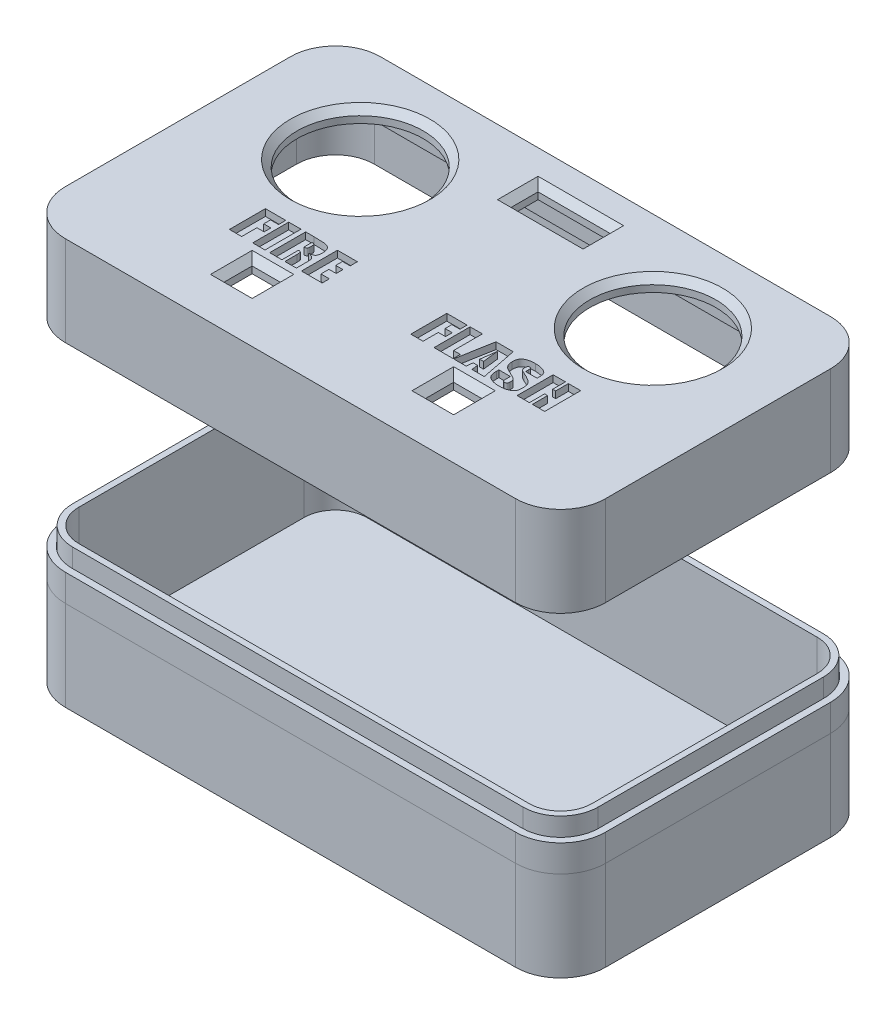
SolidWorks part; units mm, degrees
ref_plane "Front Plane" through (0, 0, 0) normal (0, 0, 1) x (1, 0, 0)
ref_plane "Top Plane" through (0, 0, 0) normal (0, 1, 0) x (1, 0, 0)
ref_plane "Right Plane" through (0, 0, 0) normal (1, 0, 0) x (0, 0, -1)
sketch "Sketch1" plane through (0, 0, 0) normal (0, 1, 0) x (1, 0, 0)
  line L1 (-60, 35) -> (60, 35)
  line L2 (-60, 35) -> (-60, -35)
  line L3 (-60, -35) -> (60, -35)
  line L4 (60, 35) -> (60, -35)
  line L5 (-60, 35) -> (60, -35) construction
  line L6 (-60, -35) -> (60, 35) construction
  point P0 (0, 0)
  dimension "D1" = 120
  dimension "D2" = 70
extrude "Boss-Extrude1" add sketch "Sketch1" along normal blind 20
fillet "Fillet1" radius 10 4 edges at (-60, 10, -35) (60, 10, -35) (60, 10, 35) (-60, 10, 35)
shell "Shell1" thickness 3 removed face at (0, 0, 0)
sketch "Sketch2" plane through (0, 20, 0) normal (0, 1, 0) x (1, 0, 0)
  line L0 (50, 35) -> (-50, 35) construction
  line L13 (-25.5, -18) -> (-19.25, -18)
  line L14 (-25.5, -18) -> (-25.5, -24.25)
  line L15 (-25.5, -24.25) -> (-19.25, -24.25)
  line L16 (-19.25, -18) -> (-19.25, -24.25)
  line L17 (-25.5, -18) -> (-19.25, -24.25) construction
  line L18 (-25.5, -24.25) -> (-19.25, -18) construction
  line L19 (19.25, -18) -> (25.5, -18)
  line L20 (19.25, -18) -> (19.25, -24.25)
  line L21 (19.25, -24.25) -> (25.5, -24.25)
  line L22 (25.5, -18) -> (25.5, -24.25)
  line L23 (19.25, -18) -> (25.5, -24.25) construction
  line L24 (19.25, -24.25) -> (25.5, -18) construction
  circle A0 centre (-32.5, 13) radius 14
  circle A1 centre (32.5, 13) radius 14
  point P0 (-32.5, 13)
  point P5 (32.5, 13)
  point P10 (-22.375, -21.125)
  point P15 (22.375, -21.125)
  dimension "D1" = 28
  dimension "D2" = 28
  dimension "D5" = 6.25
  dimension "D7" = 18
  dimension "D3" = 65
  dimension "D4" = 32.5
  dimension "D6" = 22
  dimension "D8" = 38.5
  dimension "D9" = 19.25
extrude "Cut-Extrude1" cut sketch "Sketch2" against normal up to next
sketch "Sketch5" plane through (0, 0, 0) normal (0, -1, 0) x (1, 0, 0)
  line L28 (50, 33.65) -> (-50, 33.65)
  line L29 (-58.65, 25) -> (-58.65, -25)
  line L30 (-50, -33.65) -> (50, -33.65)
  line L31 (58.65, -25) -> (58.65, 25)
  line L32 (50, 33.65) -> (-50, 33.65)
  line L33 (-58.65, 25) -> (-58.65, -25)
  line L34 (-50, -33.65) -> (50, -33.65)
  line L35 (58.65, -25) -> (58.65, 25)
  arc A23 (58.65, 25) -> (50, 33.65) centre (50, 25) ccw
  arc A24 (-50, 33.65) -> (-58.65, 25) centre (-50, 25) ccw
  arc A25 (-58.65, -25) -> (-50, -33.65) centre (-50, -25) ccw
  arc A26 (50, -33.65) -> (58.65, -25) centre (50, -25) ccw
  arc A27 (58.65, 25) -> (50, 33.65) centre (50, 25) ccw
  arc A28 (-50, 33.65) -> (-58.65, 25) centre (-50, 25) ccw
  arc A29 (-58.65, -25) -> (-50, -33.65) centre (-50, -25) ccw
  arc A30 (50, -33.65) -> (58.65, -25) centre (50, -25) ccw
  dimension "D1" = 1.35
extrude "Cut-Extrude3" cut sketch "Sketch5" against normal blind 10
ref_plane "Plane1" through (0, -40.15, 0) normal (0, -1, 0) x (-1, 0, 0)
sketch "Sketch6" plane through (0, -40.15, 0) normal (0, -1, 0) x (-1, 0, 0)
  line L4 (60, -25) -> (60, 25)
  line L5 (50, 35) -> (-50, 35)
  line L6 (-60, 25) -> (-60, -25)
  line L7 (-50, -35) -> (50, -35)
  line L8 (60, -25) -> (60, 25)
  line L9 (50, 35) -> (-50, 35)
  line L10 (-60, 25) -> (-60, -25)
  line L11 (-50, -35) -> (50, -35)
  arc A4 (60, 25) -> (50, 35) centre (50, 25) ccw
  arc A5 (-50, 35) -> (-60, 25) centre (-50, 25) ccw
  arc A6 (-60, -25) -> (-50, -35) centre (-50, -25) ccw
  arc A7 (50, -35) -> (60, -25) centre (50, -25) ccw
  arc A8 (60, 25) -> (50, 35) centre (50, 25) ccw
  arc A9 (-50, 35) -> (-60, 25) centre (-50, 25) ccw
  arc A10 (-60, -25) -> (-50, -35) centre (-50, -25) ccw
  arc A11 (50, -35) -> (60, -25) centre (50, -25) ccw
  dimension "D1" = 0
extrude "Boss-Extrude2" add sketch "Sketch6" along normal blind 30 separate body
shell "Shell2" thickness 3 removed face at (0, -40.15, 0)
sketch "Sketch7" plane through (0, -40.15, 0) normal (0, 1, 0) x (1, 0, 0)
  line L8 (-50, -33.35) -> (50, -33.35)
  line L9 (58.35, -25) -> (58.35, 25)
  line L10 (50, 33.35) -> (-50, 33.35)
  line L11 (-58.35, 25) -> (-58.35, -25)
  line L12 (-50, -33.35) -> (50, -33.35)
  line L13 (58.35, -25) -> (58.35, 25)
  line L14 (50, 33.35) -> (-50, 33.35)
  line L15 (-58.35, 25) -> (-58.35, -25)
  line L20 (-50, -36.5) -> (50, -36.5)
  line L21 (61.5, -25) -> (61.5, 25)
  line L22 (50, 36.5) -> (-50, 36.5)
  line L23 (-61.5, 25) -> (-61.5, -25)
  line L24 (-50, -36.5) -> (50, -36.5)
  line L25 (61.5, -25) -> (61.5, 25)
  line L26 (50, 36.5) -> (-50, 36.5)
  line L27 (-61.5, 25) -> (-61.5, -25)
  arc A8 (-58.35, -25) -> (-50, -33.35) centre (-50, -25) ccw
  arc A9 (50, -33.35) -> (58.35, -25) centre (50, -25) ccw
  arc A10 (58.35, 25) -> (50, 33.35) centre (50, 25) ccw
  arc A11 (-50, 33.35) -> (-58.35, 25) centre (-50, 25) ccw
  arc A12 (-58.35, -25) -> (-50, -33.35) centre (-50, -25) ccw
  arc A13 (50, -33.35) -> (58.35, -25) centre (50, -25) ccw
  arc A14 (58.35, 25) -> (50, 33.35) centre (50, 25) ccw
  arc A15 (-50, 33.35) -> (-58.35, 25) centre (-50, 25) ccw
  arc A20 (-61.5, -25) -> (-50, -36.5) centre (-50, -25) ccw
  arc A21 (50, -36.5) -> (61.5, -25) centre (50, -25) ccw
  arc A22 (61.5, 25) -> (50, 36.5) centre (50, 25) ccw
  arc A23 (-50, 36.5) -> (-61.5, 25) centre (-50, 25) ccw
  arc A24 (-61.5, -25) -> (-50, -36.5) centre (-50, -25) ccw
  arc A25 (50, -36.5) -> (61.5, -25) centre (50, -25) ccw
  arc A26 (61.5, 25) -> (50, 36.5) centre (50, 25) ccw
  arc A27 (-50, 36.5) -> (-61.5, 25) centre (-50, 25) ccw
  dimension "D1" = 1.65
  dimension "D2" = 1.5
extrude "Cut-Extrude4" cut sketch "Sketch7" against normal blind 10
sketch "Sketch8" plane through (0, 20, 0) normal (0, 1, 0) x (1, 0, 0)
  line L0 (-60, -15) -> (60, -15) construction
  line L1 (-60, 25) -> (-60, -25) construction
  line L2 (60, -25) -> (60, 25) construction
  line L3 (-19.25, -18) -> (-25.5, -18) construction
  text T0 "           FIRE        FLASH" font "Impact" height 8
  dimension "D1" = 3
extrude "Cut-Extrude5" cut sketch "Sketch8" against normal blind 1.5
sketch "Sketch9" plane through (0, 20, -15) normal (0, -1, 0) x (-1, 0, 0)
  line L1 (-8, 13) -> (8, 13)
  line L2 (-8, 13) -> (-8, 7)
  line L3 (-8, 7) -> (8, 7)
  line L4 (8, 13) -> (8, 7)
  line L5 (-8, 13) -> (8, 7) construction
  line L6 (-8, 7) -> (8, 13) construction
  line L7 (-50, 20) -> (50, 20) construction
  point P0 (0, 10)
  dimension "D1" = 6
  dimension "D2" = 16
  dimension "D3" = 7
extrude "Cut-Extrude8" cut sketch "Sketch9" along normal up to next (3 mm away)
chamfer "Chamfer1" distance 1.5 angle 45 14 edges at (8, 20, -25) (0, 20, -28) (-8, 20, -25) (0, 20, -22) (-22.375, 20, 18) (-25.5, 20, 21.125) (-22.375, 20, 24.25) (-19.25, 20, 21.125) (22.375, 20, 18) (19.25, 20, 21.125) (22.375, 20, 24.25) (25.5, 20, 21.125) (32.5, 20, 1) (-32.5, 20, 1)
ref_plane "Plane2" through (0, -3, 0) normal (0, -1, 0) x (-1, 0, 0)
sketch "Sketch10" plane through (0, -50.15, 0) normal (0, 1, 0) x (1, 0, 0)
  line L4 (-50, -35) -> (50, -35)
  line L5 (60, -25) -> (60, 25)
  line L6 (50, 35) -> (-50, 35)
  line L7 (-60, 25) -> (-60, -25)
  line L8 (-50, -35) -> (50, -35)
  line L9 (60, -25) -> (60, 25)
  line L10 (50, 35) -> (-50, 35)
  line L11 (-60, 25) -> (-60, -25)
  line L16 (-50, -33.5) -> (50, -33.5)
  line L17 (58.5, -25) -> (58.5, 25)
  line L18 (50, 33.5) -> (-50, 33.5)
  line L19 (-58.5, 25) -> (-58.5, -25)
  line L20 (-50, -33.5) -> (50, -33.5)
  line L21 (58.5, -25) -> (58.5, 25)
  line L22 (50, 33.5) -> (-50, 33.5)
  line L23 (-58.5, 25) -> (-58.5, -25)
  arc A4 (-60, -25) -> (-50, -35) centre (-50, -25) ccw
  arc A5 (50, -35) -> (60, -25) centre (50, -25) ccw
  arc A6 (60, 25) -> (50, 35) centre (50, 25) ccw
  arc A7 (-50, 35) -> (-60, 25) centre (-50, 25) ccw
  arc A8 (-60, -25) -> (-50, -35) centre (-50, -25) ccw
  arc A9 (50, -35) -> (60, -25) centre (50, -25) ccw
  arc A10 (60, 25) -> (50, 35) centre (50, 25) ccw
  arc A11 (-50, 35) -> (-60, 25) centre (-50, 25) ccw
  arc A16 (-58.5, -25) -> (-50, -33.5) centre (-50, -25) ccw
  arc A17 (50, -33.5) -> (58.5, -25) centre (50, -25) ccw
  arc A18 (58.5, 25) -> (50, 33.5) centre (50, 25) ccw
  arc A19 (-50, 33.5) -> (-58.5, 25) centre (-50, 25) ccw
  arc A20 (-58.5, -25) -> (-50, -33.5) centre (-50, -25) ccw
  arc A21 (50, -33.5) -> (58.5, -25) centre (50, -25) ccw
  arc A22 (58.5, 25) -> (50, 33.5) centre (50, 25) ccw
  arc A23 (-50, 33.5) -> (-58.5, 25) centre (-50, 25) ccw
  dimension "D1" = 0
  dimension "D2" = 0.15
extrude "Boss-Extrude3" add sketch "Sketch10" along normal blind 6 separate body
equation "\"Case Length\"= 120"
equation "\"Case Width\"= 70"
equation "\"Top Plate Depth\"= 20"
equation "\"Button\"= 6.25"
equation "\"Joystick\"= 19.5"
equation "\"D1@Sketch1\"=\"Case Length\""
equation "\"D2@Sketch1\"=\"Case Width\""
equation "\"D1@Boss-Extrude1\"=\"Top Plate Depth\""
equation "\"D5@Sketch2\"=\"Button\""
equation "\"Bottom Depth\"= 30"
equation "\"D1@Boss-Extrude2\"=\"Bottom Depth\""
equation "\"Joystick Diameter\"= 28"
equation "\"D1@Sketch2\"=\"Joystick Diameter\""
equation "\"D2@Sketch2\"=\"Joystick Diameter\""
equation "\"D4@Sketch2\"=\"D3@Sketch2\"/2"
equation "\"D9@Sketch2\"=\"D8@Sketch2\"/2"
